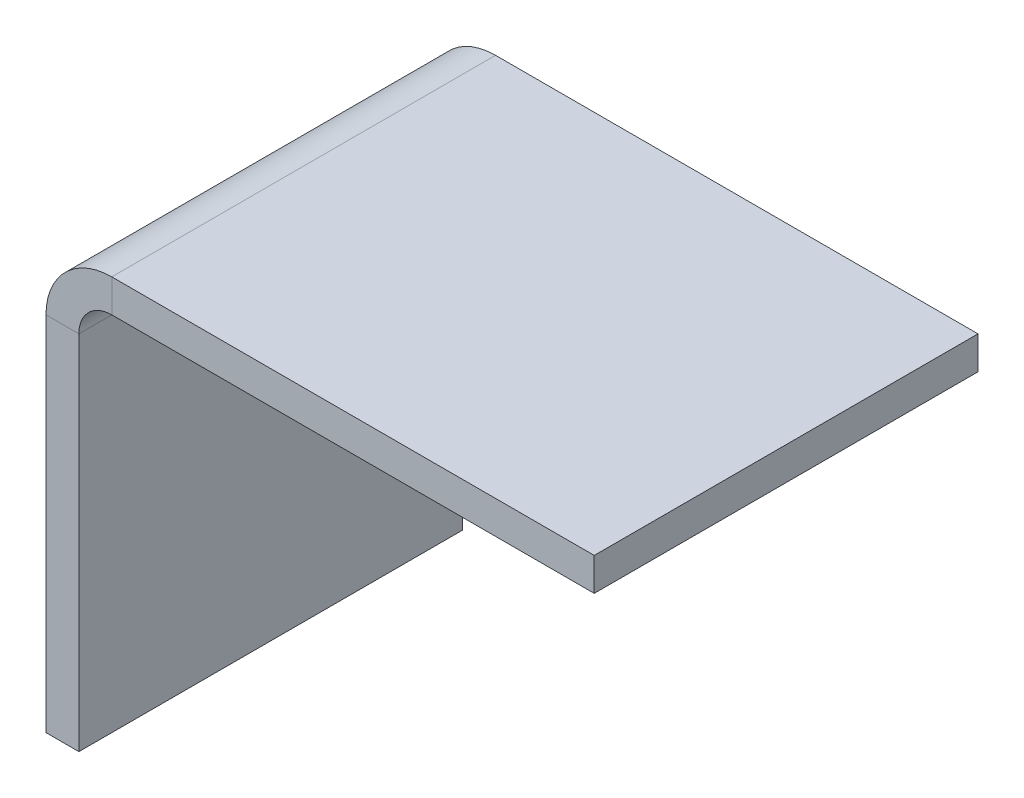
SolidWorks part; units mm, degrees
note: The reader was unsure of these and kept them because the rebuilt part matched: flange length of "Edge-Flange1".
ref_plane "Front Plane" through (0, 0, 0) normal (0, 0, 1) x (1, 0, 0)
ref_plane "Top Plane" through (0, 0, 0) normal (0, 1, 0) x (1, 0, 0)
ref_plane "Right Plane" through (0, 0, 0) normal (1, 0, 0) x (0, 0, -1)
sketch "Sketch1" plane through (0, 0, 0) normal (1, 0, 0) x (0, 0, -1)
  line L1 (-1731.2332, 342.3351) -> (-1696.2332, 342.3351)
  line L2 (-1731.2332, 342.3351) -> (-1731.2332, 375.3351)
  line L3 (-1731.2332, 375.3351) -> (-1696.2332, 375.3351)
  line L4 (-1696.2332, 342.3351) -> (-1696.2332, 375.3351)
  point P6 (0, 0)
  point P7 (0, 0)
  dimension "D1" = 33
  dimension "D2" = 35
base flange "Base-Flange1" sketch "Sketch1" thickness 3 reverse thickness direction no parameters "D1"=0.7366
edge flange "Edge-Flange1" sketch "Sketch8" flange angle 90 flange length 50 flange position bend outside bend radius 3 thickness 3 relief rectangular parameters "D6"=10
sketch "Sketch8" plane through (0, 375.3351, 0) normal (0, 1, 0) x (0, 0, 1)
  line L0 (1696.2332, 0) -> (1731.2332, 0) construction
  line L1 (1696.2332, 0) -> (1731.2332, 0)
  line L2 (1696.2332, 0) -> (1696.2332, 47)
  line L3 (1696.2332, 47) -> (1731.2332, 47)
  line L4 (1731.2332, 47) -> (1731.2332, 0)
bend "EdgeBend1" bend radius 3 bend angle 90 parameters "D5"=1
sketch "Bend-Lines1" [suppressed] plane through (0, 0, 0) normal (0, 1, 0) x (1, 0, 0)
sketch "Bounding-Box1" [suppressed] plane through (0, 0, 0) normal (0, 1, 0) x (1, 0, 0)
sheet metal parameters "Sheet-Metal1" thickness 3 parameters "D1"=0.7366
flat pattern "Flat-Pattern1" [suppressed]
sketch "Bend-Lines2" plane through (0, 0, 0) normal (0, 1, 0) x (1, 0, 0)
sketch3d "Bounding-Box2" [suppressed]
  line L0 (1845, 400, 0) -> (1845, 362.7, 0) construction
  line L1 (1810, 400, 0) -> (1810, 362.7, 0) construction
  line L2 (1845, 400, 0) -> (1810, 400, 0) construction
  line L3 (1845, 362.7, 0) -> (1810, 362.7, 0) construction
sheet metal parameters "Sheet-Metal2" thickness 3 parameters "D1"=0.7366
flat pattern "Flat-Pattern1"
sketch "Bend-Lines2" plane through (0, 0, 0) normal (1, 0, 0) x (0, 0, -1)
  line L0 (-1810, 403.2987) -> (-1845, 403.2987) construction
  line L1 (-1810, 403.2987) -> (-1845, 403.2987) construction
sketch3d "Bounding-Box2" [suppressed]
  line L0 (-1845, 450.5973, 0) -> (-1845, 362.7, 0) construction
  line L1 (-1810, 450.5973, 0) -> (-1810, 362.7, 0) construction
  line L2 (-1845, 450.5973, 0) -> (-1810, 450.5973, 0) construction
  line L3 (-1845, 362.7, 0) -> (-1810, 362.7, 0) construction
bend of the flat pattern "Flatten-<EdgeBend1>1"
